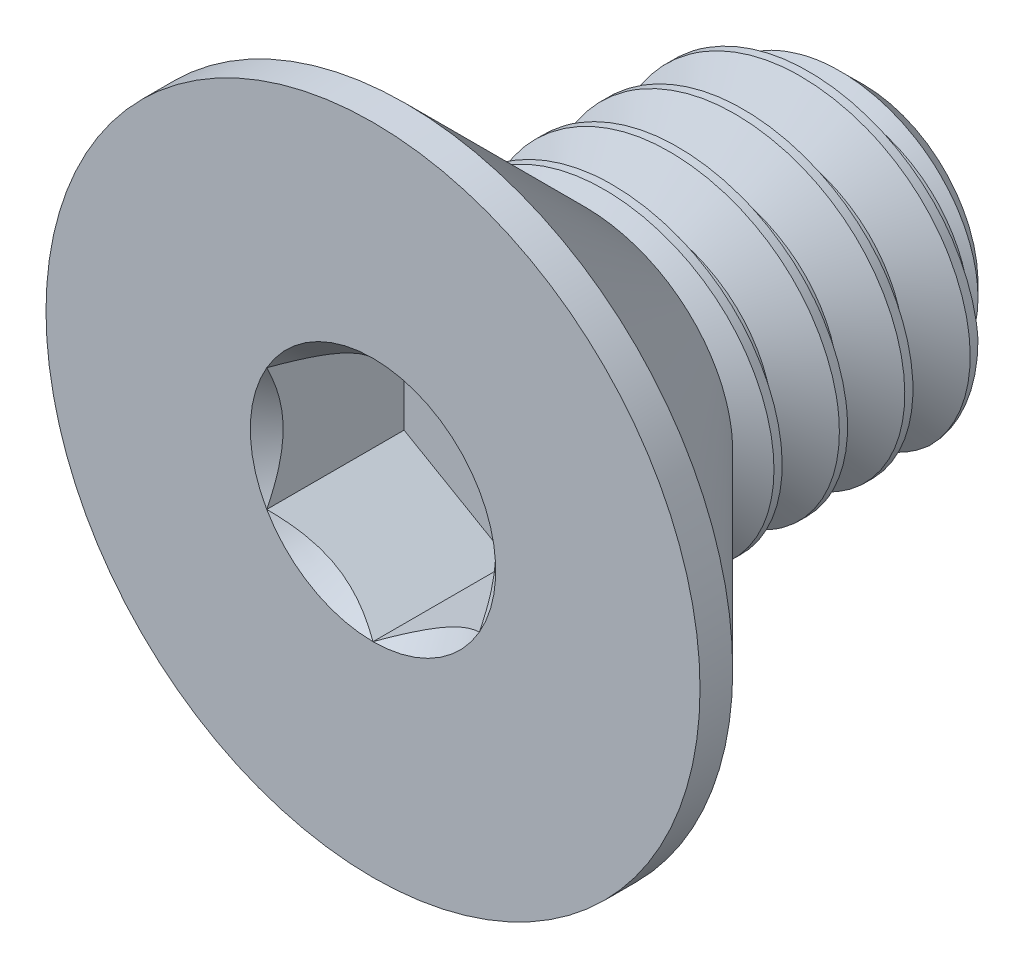
SolidWorks part; units mm, degrees
ref_plane "Front" through (0, 0, 0) normal (0, 0, 1) x (1, 0, 0)
ref_plane "Top" through (0, 0, 0) normal (0, 1, 0) x (1, 0, 0)
ref_plane "Right" through (0, 0, 0) normal (1, 0, 0) x (0, 0, -1)
sketch "Sketch1" plane through (0, 0, 0) normal (1, 0, 0) x (0, 0, -1)
  line L0 (0, 2) -> (0.2, 2) construction
  line L1 (0.2, 2) -> (1.2, 1) construction
  line L2 (0, 1) -> (3, 1)
  line L3 (3, 1) -> (3, 0)
  line L4 (3, 0) -> (0, 0)
  line L5 (0, 0) -> (0, 2) construction
  line L6 (0, 2) -> (0, -2) construction
  line L7 (3, 1) -> (3, -1) construction
  line L8 (0, -2) -> (0.2, -2) construction
  line L9 (0.2, -2) -> (1.2, -1) construction
  line L11 (0, 1) -> (0, 0)
  line L12 (1.2, 1) -> (1.2, 0) construction
  dimension "Head Ht" = 1.2
  dimension "Head Dia" = 4
  dimension "Dia" = 2
  dimension "Lg" = 3
  dimension "Head Angle" = 90
revolve "Revolve1" add sketch "Sketch1" angle 360 mid plane about L4
sketch "Sketch3" plane through (0, 0, -3) normal (0, 0, -1) x (-1, 0, 0)
  circle A0 centre (0, 0) radius 1
curve "Helix/Spiral1" pitch 0.4 height 3 radius 1 centre (0, 0, -3) axis (0, 0, 1) start towards (0, 1, 0)
sketch "Sketch2" plane through (0, 0, 0) normal (1, 0, 0) x (0, 0, -1)
  line L0 (3, 1) -> (3.35, 1)
  line L1 (3.35, 1) -> (3.2, 0.7402)
  line L2 (3.2, 0.7402) -> (3.15, 0.7402)
  line L3 (3.15, 0.7402) -> (3, 1)
  line L4 (3.075, 0.8701) -> (3.275, 0.8701) construction
  dimension "D1" = 60
  dimension "D2" = 0.05
  dimension "D3" = 0.2
chamfer "Chamfer1" distance 0.3 angle 45 1 edges at (0, 1, -3)
sweep "Cut-Sweep1" cut profiles "Sketch2" path "Helix/Spiral1" align with end faces yes
sketch "Sketch7" plane through (0, 0, 0) normal (1, 0, 0) x (0, 0, -1)
  line L0 (0, 2) -> (0.2, 2) construction
  line L1 (0.2, 2) -> (1.2, 1) construction
  line L2 (0, 2) -> (0.2, 2)
  line L3 (0.2, 2) -> (1.2, 1)
  line L4 (1.2, 1) -> (1.2, 0) construction
  line L5 (1.2, 1) -> (1.2, 0)
  line L7 (0, 0) -> (0, 2) construction
  line L8 (0, 0) -> (0, 2)
  line L9 (0, 0) -> (1.2, 0)
  line L10 (2.2, 0) -> (-2.2, 0) construction
revolve "Revolve2" add sketch "Sketch7" angle 360 mid plane about L9
ref_plane "Plane1" through (0, 0, -1.2) normal (0, 0, 1) x (1, 0, 0)
sketch "Sketch8" plane through (0, 0, -1.2) normal (0, 0, 1) x (1, 0, 0)
  circle A0 centre (0, 0) radius 1
extrude "Boss-Extrude1" add sketch "Sketch8" against normal through all draft 45
sketch "Sketch5" plane through (0, 0, 0) normal (0, 0, 1) x (1, 0, 0)
  line L1 (0.65, -0.3753) -> (0.65, 0.3753)
  line L2 (0.65, 0.3753) -> (0, 0.7506)
  line L3 (0, 0.7506) -> (-0.65, 0.3753)
  line L4 (-0.65, 0.3753) -> (-0.65, -0.3753)
  line L5 (-0.65, -0.3753) -> (0, -0.7506)
  line L6 (0, -0.7506) -> (0.65, -0.3753)
  circle A0 centre (0, 0) radius 0.65 construction
  dimension "Hex" = 1.3
extrude "Cut-Extrude2" cut sketch "Sketch5" against normal blind 0.84
sketch "Sketch6" plane through (0, 0, 0) normal (0, 0, 1) x (1, 0, 0)
  circle A0 centre (0, 0) radius 0.7506
extrude "Cut-Extrude3" cut sketch "Sketch6" against normal blind 0.84 draft 45
sketch "Sketch9" [suppressed] plane through (0, 0, -5.5) normal (0, 0, 1) x (1, 0, 0)
  circle A1 centre (0, 0) radius 5
  circle A2 centre (0, 0) radius 5
  point P0 (0, 5)
  dimension "D1" = 0
extrude "Boss-Extrude2" [suppressed] add sketch "Sketch9" against normal offset from surface (18.5 mm away) 26 up to face at (0, 0.7, -3)
fillet "Fillet1" [suppressed] radius 0.2
sketch "Sketch10" plane through (0, 0, 0) normal (1, 0, 0) x (0, 0, -1)
  line L0 (3, 1) -> (3, -1) construction
  point P0 (2.4, -1)
  dimension "D1" = 0.6
equation "\"D3@Helix/Spiral1\" = \"Lg@Sketch1\""
equation "\"D2@Sketch2\" = \"D4@Helix/Spiral1\" * .125"
equation "\"D3@Sketch2\" = \"D4@Helix/Spiral1\" * .5"
equation "\"D1@Chamfer1\" = \"D4@Helix/Spiral1\" * .75"
equation "\"D1@Cut-Extrude2\" = \"Head Ht@Sketch1\" * .7"
equation "\"D1@Sketch10\" = \"D4@Helix/Spiral1\" * 1.5"
equation "\"D1@Cut-Extrude3\" = \"D1@Cut-Extrude2\""
equation "\"D1@Fillet1\" = \"Dia@Sketch1\" * .1"
